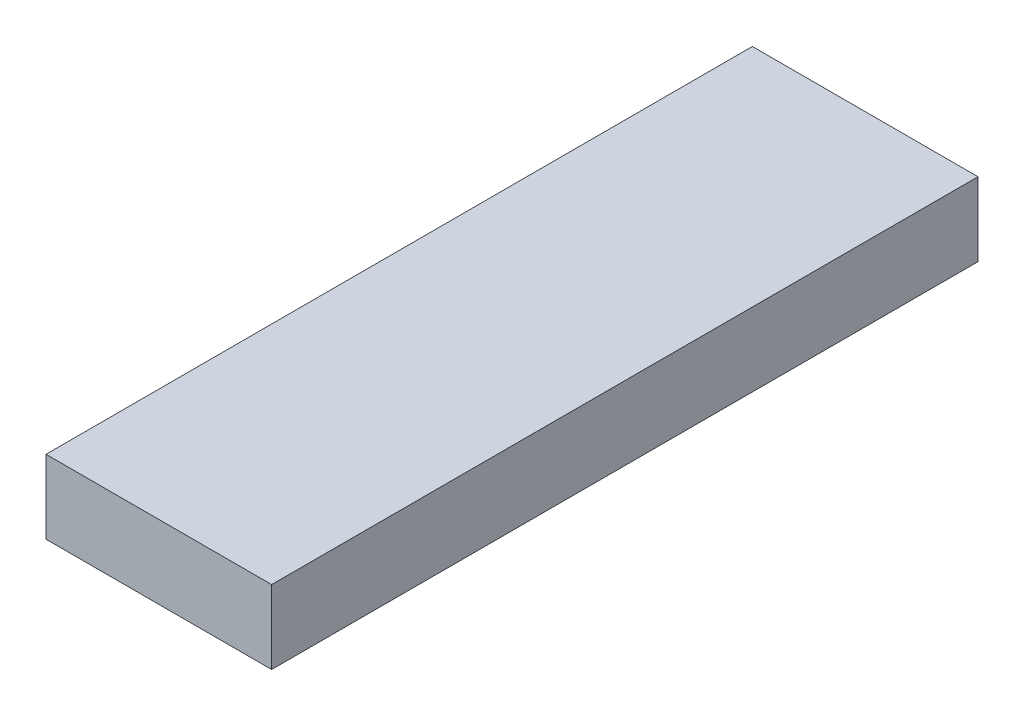
SolidWorks part; units mm, degrees
ref_plane "Front Plane" through (0, 0, 0) normal (0, 0, 1) x (1, 0, 0)
ref_plane "Top Plane" through (0, 0, 0) normal (0, 1, 0) x (1, 0, 0)
ref_plane "Right Plane" through (0, 0, 0) normal (1, 0, 0) x (0, 0, -1)
sketch "Sketch1" plane through (0, 0, 0) normal (0, 1, 0) x (1, 0, 0)
  line L2 (-23, 72) -> (23, 72)
  line L5 (-19, 72) -> (-19, 90)
  line L6 (-19, 90) -> (-4, 90)
  line L7 (-4, 90) -> (-4, 72)
  line L8 (4, 72) -> (4, 90)
  line L9 (4, 90) -> (19, 90)
  line L10 (19, 90) -> (19, 72)
  line L11 (0, 72) -> (0, 180.6197) construction
  line L13 (23, -72) -> (-23, -72)
  line L14 (23, -72) -> (23, 72)
  line L16 (-23, -72) -> (-23, 72)
  line L17 (23, -72) -> (-23, 72) construction
  line L18 (23, 72) -> (-23, -72) construction
  point P0 (0, 0)
  point P16 (-11.5, 90)
  point P17 (11.5, 90)
  dimension "D1" = 144
  dimension "D2" = 46
  dimension "D3" = 15
  dimension "D4" = 23
  dimension "D5" = 18
extrude "Boss-Extrude1" add sketch "Sketch1" along normal blind 15 contours L2 L14 L13 L16
